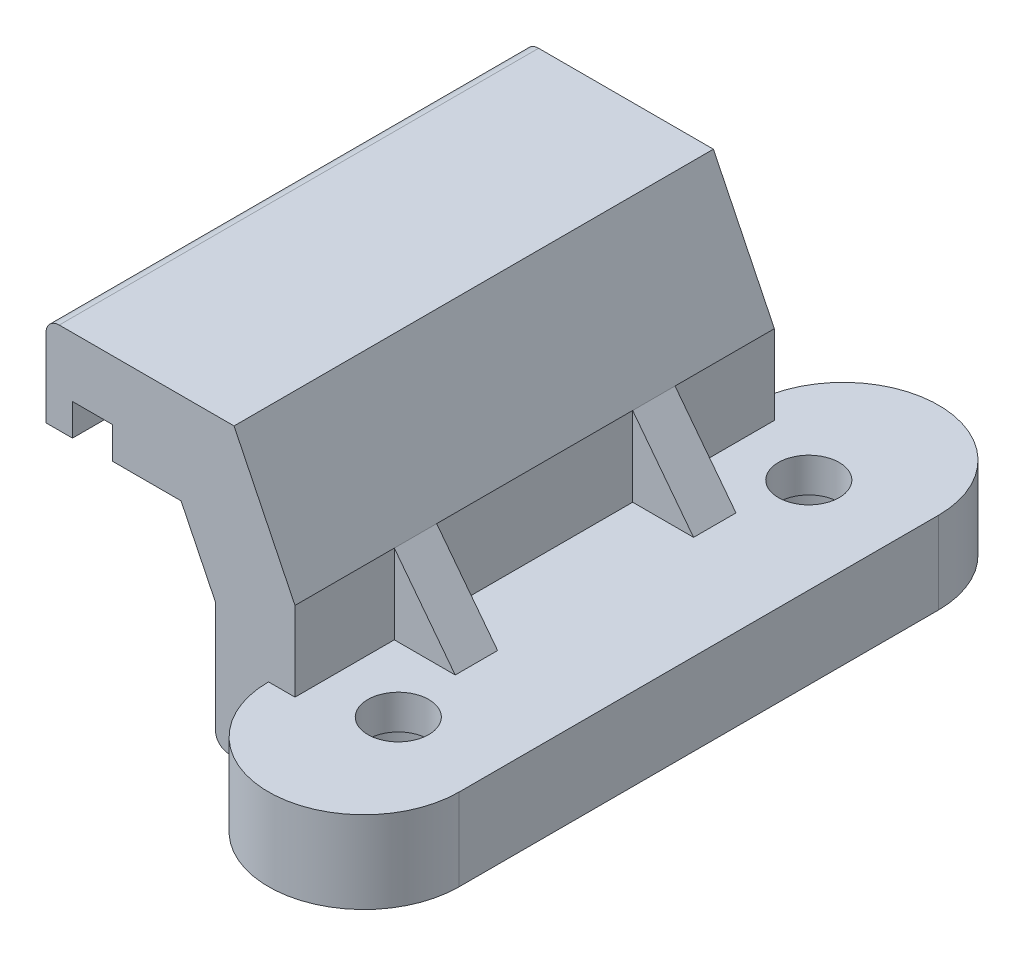
SolidWorks part; units mm, degrees
ref_plane "Plan de face" through (0, 0, 0) normal (0, 0, 1) x (1, 0, 0)
ref_plane "Plan de dessus" through (0, 0, 0) normal (0, 1, 0) x (1, 0, 0)
ref_plane "Plan de droite" through (0, 0, 0) normal (1, 0, 0) x (0, 0, -1)
sketch "Esquisse1" plane through (0, 0, 0) normal (0, 0, 1) x (1, 0, 0)
  line L0 (0.5, 0) -> (9.2, 0)
  line L1 (9.2, 0) -> (9.2, 3.1)
  line L2 (9.2, 3.1) -> (3, 3.1)
  line L3 (3, 3.1) -> (3, 6.1)
  line L4 (3, 6.1) -> (0.6983, 10.8185)
  line L5 (0.6983, 10.8185) -> (-5.9017, 10.8185)
  line L6 (-6.4017, 10.3185) -> (-6.4017, 7.3685)
  line L7 (-6.4017, 7.3685) -> (-5.4017, 7.3685)
  line L8 (-5.4017, 7.3685) -> (-5.4017, 8.5685)
  line L9 (-5.4017, 8.5685) -> (-3.8847, 8.5685)
  line L10 (-3.8847, 8.5685) -> (-3.8847, 7.3685)
  line L11 (-3.8847, 7.3685) -> (-1.3017, 7.3685)
  line L12 (-1.3017, 7.3685) -> (0, 4.7)
  line L13 (0, 4.7) -> (0, 0.5)
  arc A2 (-5.9017, 10.8185) -> (-6.4017, 10.3185) centre (-5.9017, 10.3185) ccw
  arc A3 (0.5, 0) -> (0, 0.5) centre (0.5, 0.5) cw
  point P23 (-6.4017, 10.8185)
  point P26 (0, 0)
  dimension "D1" = 3.1
  dimension "D2" = 9.2
  dimension "D3" = 3
  dimension "D4" = 3
  dimension "D5" = 4.7
  dimension "D6" = 1
  dimension "D7" = 1.2
  dimension "D9" = 3.45
  dimension "D11" = 9.4017
  dimension "D14" = 5.25
extrude "Extrusion1" add sketch "Esquisse1" along normal blind 18.1
shell "Coque1" thickness 1 removed face at (-2.5932, 7.3685, 9.05) removed face at (0, 2.6, 9.05) removed face at (-0.6509, 6.0343, 9.05) removed face at (0.1982, 0.1982, 9.05) removed face at (4.85, 0, 9.05)
sketch "Esquisse2" plane through (0, 3.1, 0) normal (0, 1, 0) x (-1, 0, 0)
  line L0 (-9.2, 0) -> (-2, 0)
  line L1 (-3, 0) -> (-0.6983, 0) construction
  line L2 (-9.2, 9.05) -> (-2, 9.05) construction
  line L3 (-9.2, 18.1) -> (-2, 18.1)
  line L5 (-9.2, 18.1) -> (-9.2, 0) construction
  arc A0 (-9.2, 0) -> (-2, 0) centre (-5.6, 0) ccw
  arc A1 (-9.2, 18.1) -> (-2, 18.1) centre (-5.6, 18.1) cw
  dimension "D1" = 7.2
extrude "Extrusion2" add sketch "Esquisse2" against normal up to surface (3.1 mm away) up to face at (4.6, 0, 9.05)
sketch "Esquisse3" plane through (0, 0, 0) normal (0, -1, 0) x (1, 0, 0)
  line L0 (8.2, 17.1) -> (8.2, 1) construction
  line L1 (2, 0) -> (8.2, 0)
  line L2 (2, 0) -> (2, 18.1)
  line L3 (2, 18.1) -> (8.2, 18.1)
  line L4 (8.2, 0) -> (8.2, 18.1)
  line L5 (2, 17.1) -> (2, 1) construction
extrude "Extrusion3" add sketch "Esquisse3" against normal up to surface (2.1 mm away) up to face at (5.1, 2.1, 9.05)
hole_wizard "Chambrage pour vis à tête hexagonale M2.51" positions "Esquisse5" profile "Esquisse4" counterbore size "M2.5" standard "ISO" end condition through all
sketch "Esquisse5" plane through (0, 0, 0) normal (0, -1, 0) x (1, 0, 0)
  line L0 (9.2, 18.1) -> (9.2, 0) construction
  arc A2 (9.2, 18.1) -> (2, 18.1) centre (5.6, 18.1) ccw construction
  point P0 (5.6, 1.3)
  point P1 (5.6, 16.8)
  dimension "D2" = 1.3
  dimension "D1" = 15.5
  dimension "D3" = 3.6
sketch "Esquisse4" plane through (5.6, 0, 1.3) normal (1, 0, 0) x (0, 0, -1)
  line L0 (0, 0) -> (0, 10.8185)
  line L1 (0, 10.8185) -> (1.15, 10.8185)
  line L3 (1.15, 10.8185) -> (1.15, 1.8)
  line L4 (1.15, 1.8) -> (2.25, 1.8)
  line L5 (2.25, 1.8) -> (2.25, 0)
  line L7 (2.25, 0) -> (0, 0)
  line L11 (0, -6.35) -> (0, 107.95) construction
  dimension "Diamètre du perçage jusqu'au prochain" = 2.3
  dimension "Profondeur du perçage jusqu'au prochain" = 10.8185
  dimension "Diamètre du chambrage" = 4.5
  dimension "Profondeur du chambrage" = 1.8
sketch "Esquisse6" plane through (0, 0, 0) normal (0, -1, 0) x (1, 0, 0)
  line L0 (5.6, 16.8) -> (5.6, 1.3) construction
  line L1 (3.75, 4.9) -> (7.45, 4.9)
  line L2 (3.25, 5.4) -> (3.25, 12.7)
  line L3 (3.75, 13.2) -> (7.45, 13.2)
  line L4 (7.95, 5.4) -> (7.95, 12.7)
  line L5 (1.0813, 9.05) -> (10.1187, 9.05) construction
  arc A1 (7.95, 12.7) -> (7.45, 13.2) centre (7.45, 12.7) ccw
  arc A2 (7.45, 4.9) -> (7.95, 5.4) centre (7.45, 5.4) ccw
  arc A3 (3.75, 4.9) -> (3.25, 5.4) centre (3.75, 5.4) cw
  arc A4 (3.75, 13.2) -> (3.25, 12.7) centre (3.75, 12.7) ccw
  circle A5 centre (5.6, 1.3) radius 1.15 construction
  point P8 (7.95, 4.9)
  point P11 (3.25, 4.9)
  point P14 (3.25, 13.2)
  point P20 (5.6, 9.05)
  dimension "D3" = 0.5
  dimension "D1" = 4.7
  dimension "D2" = 8.3
extrude "Enlèv. mat.-Extru.1" cut sketch "Esquisse6" against normal blind 1.6
ref_plane "Plan1" through (0, 0, 14.35) normal (0, 0, 1) x (1, 0, 0)
sketch "Esquisse7" plane through (0, 0, 14.35) normal (0, 0, 1) x (1, 0, 0)
  line L0 (3, 6.1) -> (5.3, 3.1)
  line L1 (9.2, 3.1) -> (2, 3.1) construction
  line L2 (5.3, 3.1) -> (3, 3.1)
  line L3 (3, 3.1) -> (3, 6.1)
  dimension "D1" = 2.3
extrude "Extrusion4" add sketch "Esquisse7" against normal blind 1.6
pattern_linear "Répétition linéaire1" count 2 spacing 9 along (0, 0, -1) of "Extrusion4"
